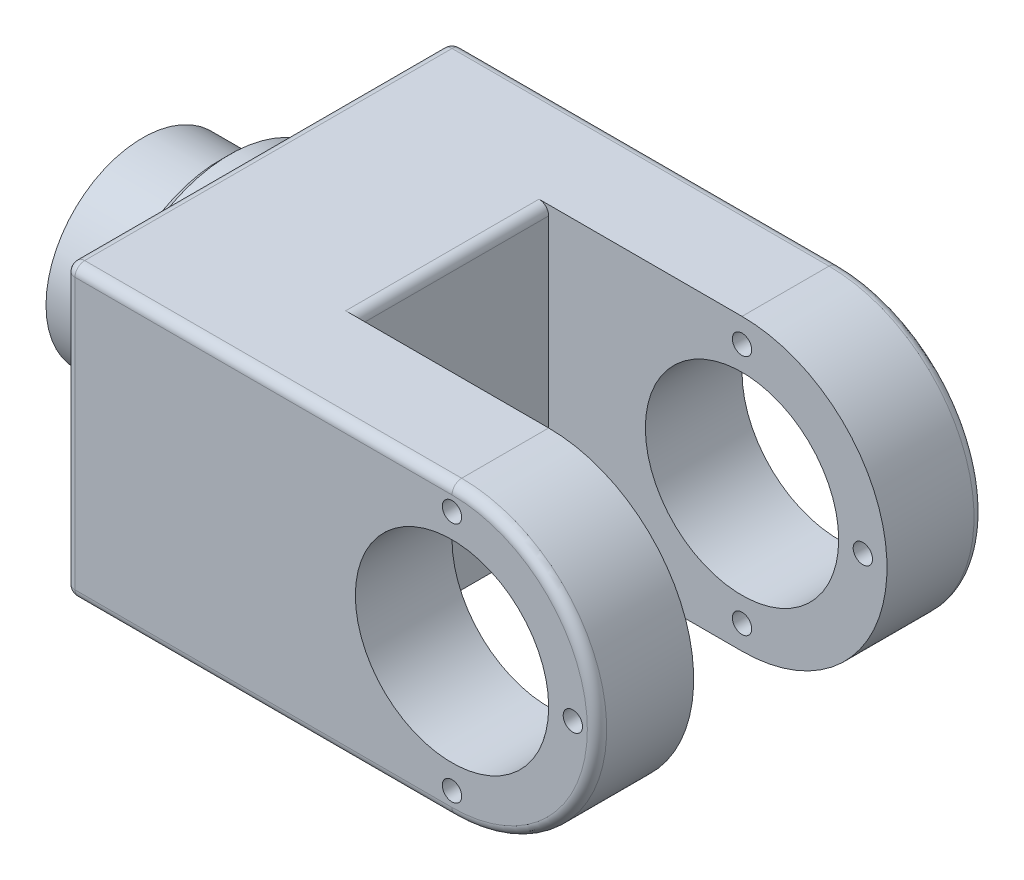
SolidWorks part; units mm, degrees
ref_plane "Front Plane" through (0, 0, 0) normal (0, 0, 1) x (1, 0, 0)
ref_plane "Top Plane" through (0, 0, 0) normal (0, 1, 0) x (1, 0, 0)
ref_plane "Right Plane" through (0, 0, 0) normal (1, 0, 0) x (0, 0, -1)
sketch "Sketch1" plane through (0, 0, 0) normal (0, 0, 1) x (1, 0, 0)
  line L1 (0, -75) -> (-200, -75)
  line L3 (0, 75) -> (-200, 75)
  line L4 (-200, -75) -> (-200, 75)
  arc A0 (0, -75) -> (0, 75) centre (0, 0) ccw
  point P7 (0, 75)
  dimension "D1" = 150
  dimension "D2" = 200
extrude "Boss-Extrude1" add sketch "Sketch1" along normal mid plane 200
sketch "Sketch2" plane through (0, 75, 0) normal (0, 1, 0) x (1, 0, 0)
  line L0 (0, -100) -> (0, 100) construction
  line L1 (100, -50) -> (-100, -50)
  line L2 (100, -50) -> (100, 50)
  line L3 (100, 50) -> (-100, 50)
  line L4 (-100, -50) -> (-100, 50)
  line L5 (100, -50) -> (-100, 50) construction
  line L6 (100, 50) -> (-100, -50) construction
  point P0 (0, 0)
  dimension "D1" = 100
  dimension "D2" = 100
extrude "Cut-Extrude1" cut sketch "Sketch2" against normal through all
sketch "Sketch3" plane through (-200, 0, 0) normal (-1, 0, 0) x (0, 0, 1)
  circle A0 centre (0, 0) radius 65
  dimension "D1" = 130
extrude "Boss-Extrude2" add sketch "Sketch3" along normal blind 20 contours A0
sketch "Sketch4" plane through (-220, 0, 0) normal (-1, 0, 0) x (0, 0, 1)
  circle A0 centre (0, 0) radius 50
  dimension "D1" = 100
extrude "Boss-Extrude3" add sketch "Sketch4" along normal blind 40
chamfer "Chamfer1" distance 5 angle 45 1 edges at (-220, 0, 65)
sketch "Sketch5" plane through (0, 0, 100) normal (0, 0, 1) x (1, 0, 0)
  circle A0 centre (0, 0) radius 62.5 construction
  circle A1 centre (0, 62.5) radius 5
  circle A2 centre (0, -62.5) radius 5
  circle A3 centre (62.5, 0) radius 5
  circle A4 centre (0, 0) radius 50
  dimension "D1" = 10
  dimension "D2" = 125
  dimension "D3" = 100
extrude "Cut-Extrude2" cut sketch "Sketch5" against normal through all
fillet "Fillet1" radius 5 13 edges at (-100, -75, -100) (75, 0, -100) (-100, -75, 100) (75, 0, 100) (-220, 0, 50) (-200, 0, 65) (-200, -75, 0) (-200, 0, 100) (-200, 0, -100) (-200, 75, 0) (-100, 75, -100) (-100, 75, 0) (-100, 75, 100)
